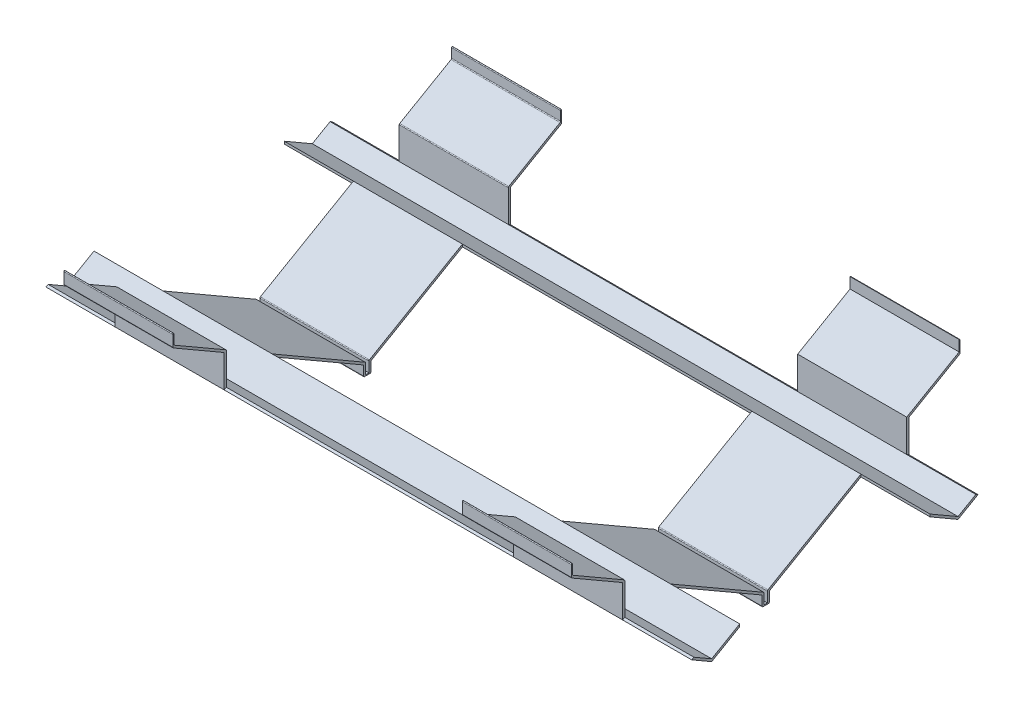
SolidWorks part; units mm, degrees
ref_plane "Front Plane" through (0, 0, 0) normal (0, 0, 1) x (1, 0, 0)
ref_plane "Top Plane" through (0, 0, 0) normal (0, 1, 0) x (1, 0, 0)
ref_plane "Right Plane" through (0, 0, 0) normal (1, 0, 0) x (0, 0, -1)
sketch "Sketch1" plane through (0, 0, 0) normal (1, 0, 0) x (0, 0, -1)
  line L1 (-7.5, 5) -> (7.5, 5)
  line L2 (7.5, 5) -> (7.5, 55)
  line L3 (7.5, 55) -> (440.5127, 305)
  line L4 (440.5127, 305) -> (570.4165, 230)
  line L5 (570.4165, 230) -> (652.6889, 277.5)
  line L6 (652.6889, 277.5) -> (652.6889, 427.5)
  line L7 (652.6889, 427.5) -> (895.176, 567.5)
  line L8 (895.176, 567.5) -> (895.176, 617.5)
  line L9 (895.176, 617.5) -> (900.176, 617.5)
  line L10 (900.176, 617.5) -> (900.176, 558.8397)
  line L11 (900.176, 558.8397) -> (662.6889, 421.7265)
  line L12 (662.6889, 421.7265) -> (662.6889, 271.7265)
  line L13 (662.6889, 271.7265) -> (570.4165, 218.453)
  line L14 (570.4165, 218.453) -> (440.5127, 293.453)
  line L15 (440.5127, 293.453) -> (17.5, 49.2265)
  line L16 (17.5, 49.2265) -> (17.5, 0)
  line L17 (17.5, 0) -> (-17.5, 0)
  line L18 (0, -6.3719) -> (0, 0) construction
  line L19 (-17.5, 49.2265) -> (-17.5, 0)
  line L20 (-440.5127, 293.453) -> (-17.5, 49.2265)
  line L21 (-570.4165, 218.453) -> (-440.5127, 293.453)
  line L22 (-662.6889, 271.7265) -> (-570.4165, 218.453)
  line L23 (-662.6889, 421.7265) -> (-662.6889, 271.7265)
  line L24 (-900.176, 558.8397) -> (-662.6889, 421.7265)
  line L25 (-900.176, 617.5) -> (-900.176, 558.8397)
  line L26 (-895.176, 617.5) -> (-900.176, 617.5)
  line L27 (-895.176, 567.5) -> (-895.176, 617.5)
  line L28 (-652.6889, 427.5) -> (-895.176, 567.5)
  line L29 (-652.6889, 277.5) -> (-652.6889, 427.5)
  line L30 (-570.4165, 230) -> (-652.6889, 277.5)
  line L31 (-440.5127, 305) -> (-570.4165, 230)
  line L32 (-7.5, 55) -> (-440.5127, 305)
  line L33 (-7.5, 5) -> (-7.5, 55)
  line L34 (0, 5) -> (0, 23.7609) construction
  dimension "D2" = 10
  dimension "D3" = 10
  dimension "D4" = 120
  dimension "D5" = 10
  dimension "D6" = 120
  dimension "D7" = 120
  dimension "D8" = 10
  dimension "D9" = 10
  dimension "D10" = 10
  dimension "D11" = 500
  dimension "D12" = 280
  dimension "D13" = 5
  dimension "D14" = 5
  dimension "D15" = 120
  dimension "D16" = 245
  dimension "D17" = 150
  dimension "D18" = 7.5
  dimension "D19" = 50
  dimension "D20" = 50
extrude "Boss-Extrude1" add sketch "Sketch1" along normal blind 505
sketch "Sketch2" plane through (505, 0, 0) normal (1, 0, 0) x (0, 0, -1)
  line L0 (440.5127, 305) -> (570.4165, 230)
  line L1 (570.4165, 230) -> (652.6889, 277.5)
  line L2 (652.6889, 277.5) -> (662.6889, 271.7265)
  line L3 (662.6889, 271.7265) -> (570.4165, 218.453)
  line L4 (570.4165, 218.453) -> (440.5127, 293.453)
  line L5 (440.5127, 293.453) -> (440.5127, 305)
  line L6 (-652.6889, 277.5) -> (-570.4165, 230)
  line L7 (-570.4165, 230) -> (-440.5127, 305)
  line L8 (-440.5127, 305) -> (-440.5127, 293.453)
  line L9 (-440.5127, 293.453) -> (-570.4165, 218.453)
  line L10 (-570.4165, 218.453) -> (-662.6889, 271.7265)
  line L11 (-662.6889, 271.7265) -> (-652.6889, 277.5)
extrude "Boss-Extrude3" add sketch "Sketch2" along normal blind 1340 and the other way blind 825
sketch "Sketch4" plane through (1845, 0, 0) normal (1, 0, 0) x (0, 0, -1)
  line L0 (-900.176, 617.5) -> (-895.176, 617.5)
  line L1 (-895.176, 617.5) -> (-895.176, 567.5)
  line L2 (-895.176, 567.5) -> (-652.6889, 427.5)
  line L3 (-652.6889, 427.5) -> (-652.6889, 277.5)
  line L4 (-652.6889, 277.5) -> (-570.4165, 230)
  line L5 (-570.4165, 230) -> (-440.5127, 305)
  line L6 (-440.5127, 305) -> (-7.5, 55)
  line L7 (-7.5, 55) -> (-7.5, 5)
  line L8 (-7.5, 5) -> (7.5, 5)
  line L9 (7.5, 5) -> (7.5, 55)
  line L10 (7.5, 55) -> (440.5127, 305)
  line L11 (440.5127, 305) -> (570.4165, 230)
  line L12 (570.4165, 230) -> (652.6889, 277.5)
  line L13 (652.6889, 277.5) -> (652.6889, 427.5)
  line L14 (652.6889, 427.5) -> (895.176, 567.5)
  line L15 (895.176, 567.5) -> (895.176, 617.5)
  line L16 (895.176, 617.5) -> (900.176, 617.5)
  line L17 (900.176, 617.5) -> (900.176, 558.8397)
  line L18 (900.176, 558.8397) -> (662.6889, 421.7265)
  line L19 (662.6889, 421.7265) -> (662.6889, 271.7265)
  line L20 (662.6889, 271.7265) -> (570.4165, 218.453)
  line L21 (570.4165, 218.453) -> (440.5127, 293.453)
  line L22 (440.5127, 293.453) -> (17.5, 49.2265)
  line L23 (17.5, 49.2265) -> (17.5, 0)
  line L24 (17.5, 0) -> (-17.5, 0)
  line L25 (-17.5, 0) -> (-17.5, 49.2265)
  line L26 (-17.5, 49.2265) -> (-440.5127, 293.453)
  line L27 (-440.5127, 293.453) -> (-570.4165, 218.453)
  line L28 (-570.4165, 218.453) -> (-662.6889, 271.7265)
  line L29 (-662.6889, 271.7265) -> (-662.6889, 421.7265)
  line L30 (-662.6889, 421.7265) -> (-900.176, 558.8397)
  line L31 (-900.176, 558.8397) -> (-900.176, 617.5)
extrude "Boss-Extrude4" add sketch "Sketch4" along normal blind 505
sketch "Sketch5" plane through (2350, 0, 0) normal (1, 0, 0) x (0, 0, -1)
  line L0 (440.5127, 305) -> (570.4165, 230)
  line L1 (570.4165, 230) -> (652.6889, 277.5)
  line L2 (652.6889, 277.5) -> (662.6889, 271.7265)
  line L3 (662.6889, 271.7265) -> (570.4165, 218.453)
  line L4 (570.4165, 218.453) -> (440.5127, 293.453)
  line L5 (440.5127, 293.453) -> (440.5127, 305)
  line L6 (-652.6889, 277.5) -> (-570.4165, 230)
  line L7 (-570.4165, 230) -> (-440.5127, 305)
  line L8 (-440.5127, 305) -> (-440.5127, 293.453)
  line L9 (-440.5127, 293.453) -> (-570.4165, 218.453)
  line L10 (-570.4165, 218.453) -> (-662.6889, 271.7265)
  line L11 (-662.6889, 271.7265) -> (-652.6889, 277.5)
extrude "Boss-Extrude5" add sketch "Sketch5" along normal blind 320
fillet "Fillet1" radius 5 29 edges at (252.5, 617.5, -895.176) (252.5, 567.5, -895.176) (252.5, 427.5, -652.6889) (252.5, 421.7265, -662.6889) (252.5, 558.8397, -900.176) (252.5, 617.5, -900.176) (2097.5, 617.5, -900.176) (2097.5, 558.8397, -900.176) (2097.5, 421.7265, -662.6889) (252.5, 421.7265, 662.6889) (2097.5, 421.7265, 662.6889) (2097.5, 427.5, 652.6889) (252.5, 427.5, 652.6889) (252.5, 567.5, 895.176) (252.5, 617.5, 895.176) (252.5, 617.5, 900.176) (252.5, 558.8397, 900.176) (2097.5, 558.8397, 900.176) (2097.5, 567.5, 895.176) (2097.5, 617.5, 895.176) (2097.5, 617.5, 900.176) (252.5, 0, 17.5) (252.5, 0, -17.5) (252.5, 55, -7.5) (252.5, 55, 7.5) (2097.5, 0, -17.5) (2097.5, 0, 17.5) (2097.5, 55, -7.5) (2097.5, 55, 7.5)
